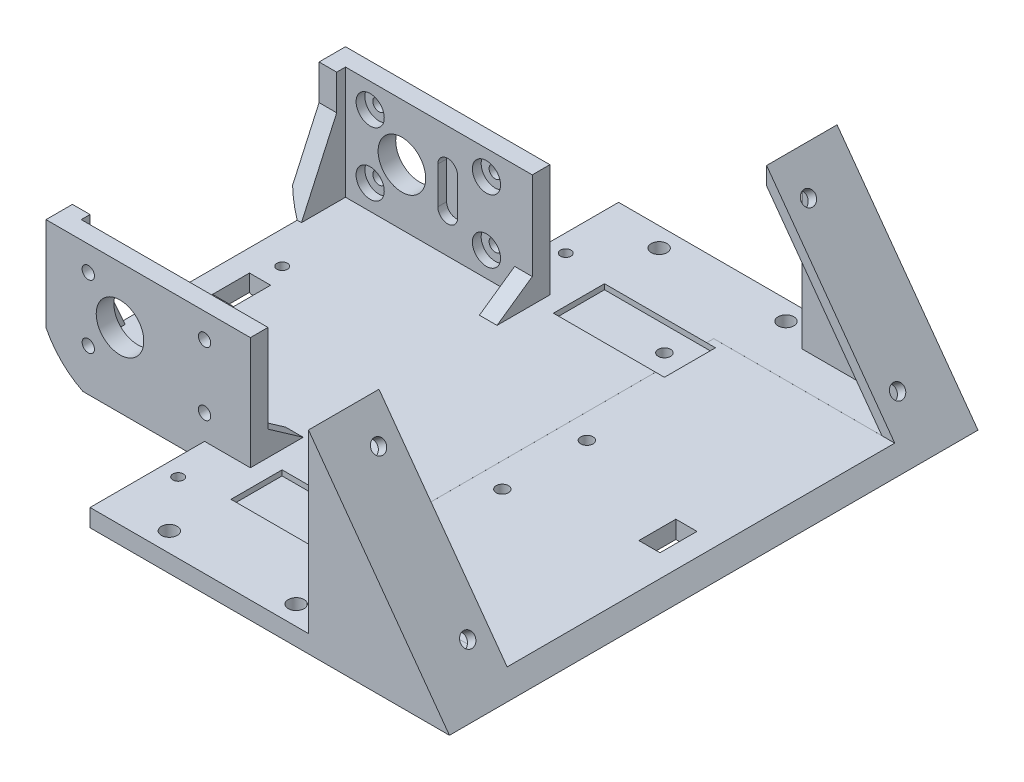
SolidWorks part; units mm, degrees
ref_plane "Front Plane" through (0, 0, 0) normal (0, 0, 1) x (1, 0, 0)
ref_plane "Top Plane" through (0, 0, 0) normal (0, 1, 0) x (1, 0, 0)
ref_plane "Right Plane" through (0, 0, 0) normal (1, 0, 0) x (0, 0, -1)
sketch "Sketch1" plane through (0, 0, 0) normal (0, 1, 0) x (1, 0, 0)
  line L0 (-25, 75) -> (-25, 42.5)
  line L1 (-25, -75) -> (77, -75)
  line L2 (-70, -42.5) -> (-70, 42.5)
  line L3 (-25, 75) -> (77, 75)
  line L4 (77, -75) -> (77, 75)
  line L7 (-25, 42.5) -> (-70, 42.5)
  line L8 (2, 0) -> (77, 0) construction
  line L9 (-25, -42.5) -> (-70, -42.5)
  line L10 (-25, -75) -> (-25, -42.5)
  point P0 (0, 0)
  dimension "D1" = 150
  dimension "D2" = 102
  dimension "D3" = 85
  dimension "D4" = 45
  dimension "D5" = 75
  dimension "D6" = 32.5
  dimension "D7" = 32.5
extrude "Boss-Extrude1" add sketch "Sketch1" along normal blind 5
sketch "Sketch3" plane through (0, 5, 0) normal (0, 1, 0) x (1, 0, 0)
  line L2 (-65, 25) -> (-70, 25)
  line L3 (-25, 42.5) -> (-70, 42.5) construction
  line L6 (-65, 25) -> (-65, 37.5)
  line L8 (0, 0) -> (-70, 0) construction
  line L9 (-70, 42.5) -> (-70, -42.5) construction
  line L17 (-65, 37.5) -> (-17, 37.5)
  line L18 (-12, 37.5) -> (-12, 42.5)
  line L19 (-12, 42.5) -> (-25, 42.5)
  line L20 (-25, 42.5) -> (-65, 42.5)
  line L28 (-12, 37.5) -> (-12, 27.5)
  line L29 (-12, 27.5) -> (-17, 27.5)
  line L30 (-17, 27.5) -> (-17, 37.5)
  line L40 (-70, -42.5) -> (-65, -42.5)
  line L41 (-70, 25) -> (-70, 42.5)
  line L42 (-70, 42.5) -> (-65, 42.5)
  line L43 (-70, -25) -> (-70, -42.5)
  line L44 (-17, -27.5) -> (-17, -37.5)
  line L45 (-12, -27.5) -> (-17, -27.5)
  line L46 (-12, -37.5) -> (-12, -27.5)
  line L47 (-25, -42.5) -> (-65, -42.5)
  line L48 (-12, -42.5) -> (-25, -42.5)
  line L49 (-12, -37.5) -> (-12, -42.5)
  line L50 (-65, -37.5) -> (-17, -37.5)
  line L51 (-65, -25) -> (-65, -37.5)
  line L52 (-65, -25) -> (-70, -25)
  line M11 (-70, -42.5) -> (-25, -42.5)
  dimension "D1" = 0
  dimension "D2" = 5
  dimension "D3" = 48
  dimension "D4" = 5
  dimension "D6" = 5
  dimension "D7" = 15
  dimension "D8" = 5
  dimension "D9" = 5
extrude "Boss-Extrude2" add sketch "Sketch3" along normal blind 32 contours M11 | L6 L17 L30 L29 L28 L18 L19 L20 L42 L41 L2 region at (-41.823, 5, 37.7096)
sketch "Sketch5" plane through (-70, 0, 0) normal (-1, 0, 0) x (0, 0, 1)
  line L0 (-25, 37) -> (-35, 37)
  line L1 (-25, 37) -> (-42.5, 37) construction
  line L2 (-35, 37) -> (-35, 27)
  line L3 (-35, 27) -> (-25, 5)
  line L4 (-25, 5) -> (-25, 37)
  line L5 (0, 0) -> (0, 35) construction
  line L6 (25, 5) -> (25, 37)
  line L7 (35, 27) -> (25, 5)
  line L8 (35, 37) -> (35, 27)
  line L9 (25, 37) -> (35, 37)
  dimension "D1" = 10
  dimension "D2" = 10
extrude "Cut-Extrude2" cut sketch "Sketch5" against normal blind 5
sketch "Sketch6" plane through (-12, 0, 0) normal (1, 0, 0) x (0, 0, -1)
  line L0 (-27.5, 37) -> (-37.5, 37)
  line L1 (-27.5, 37) -> (-42.5, 37) construction
  line L2 (-37.5, 37) -> (-37.5, 12)
  line L3 (-37.5, 12) -> (-27.5, 5)
  line L4 (-27.5, 5) -> (-27.5, 37)
  line L5 (0, 0) -> (0, 35) construction
  line L6 (37.5, 12) -> (27.5, 5)
  line L7 (37.5, 37) -> (37.5, 12)
  line L8 (27.5, 37) -> (37.5, 37)
  line L9 (27.5, 5) -> (27.5, 37)
  dimension "D1" = 10
  dimension "D2" = 25
extrude "Cut-Extrude3" cut sketch "Sketch6" against normal blind 5
sketch "Sketch7" plane through (0, 0, -42.5) normal (0, 0, -1) x (-1, 0, 0)
  line L0 (70, 37) -> (70, 0) construction
  line L1 (70, 37) -> (12, 37) construction
  line L2 (70, 37) -> (70, 0) construction
  circle A0 centre (49, 21) radius 6.75
  circle A1 centre (25, 30) radius 1.75
  circle A2 centre (25, 12) radius 1.75
  circle A3 centre (58, 30) radius 1.75
  circle A4 centre (58, 12) radius 1.75
  dimension "D1" = 21
  dimension "D2" = 13.5
  dimension "D3" = 16
  dimension "D4" = 3.5
  dimension "D5" = 7
  dimension "D6" = 12
  dimension "D7" = 3.5
  dimension "D10" = 3.5
  dimension "D12" = 3.5
  dimension "D13" = 7
  dimension "D14" = 18
  dimension "D15" = 12
  dimension "D8" = 33
  dimension "D9" = 18
  dimension "D11" = 33
extrude "Đục lỗ động cơ" cut sketch "Sketch7" against normal through all
sketch "Sketch8" plane through (0, 5, 0) normal (0, 1, 0) x (1, 0, 0)
  line L0 (77, -75) -> (77, -65)
  line L1 (77, -75) -> (77, 75) construction
  line L2 (77, -65) -> (37, -65)
  line L3 (37, -65) -> (37, -75)
  line L4 (-25, -75) -> (77, -75) construction
  line L5 (37, -75) -> (77, -75)
  line L6 (77, 0) -> (0, 0) construction
  line L7 (37, 75) -> (77, 75)
  line L8 (37, 65) -> (37, 75)
  line L9 (77, 65) -> (37, 65)
  line L10 (77, 75) -> (77, 65)
  dimension "D1" = 10
  dimension "D2" = 40
extrude "Boss-Extrude3" add sketch "Sketch8" along normal blind 55
sketch "Sketch9" plane through (0, 0, -75) normal (0, 0, -1) x (-1, 0, 0)
  line L4 (-77, 0) -> (-37, 55.0553)
  line L5 (-37, 60) -> (-37, 5) construction
  line L6 (-37, 55.0553) -> (-37, 60)
  line L7 (-37, 60) -> (-77, 60)
  line L8 (-77, 60) -> (-77, 0)
  line L9 (-77, 0) -> (25, 0) construction
  dimension "D1" = 54
extrude "Cut-Extrude5" cut sketch "Sketch9" against normal through all
sketch "Sketch10" plane through (0, 0, 0) normal (0, -1, 0) x (-1, 0, 0)
  line L0 (25, -75) -> (-77, -75) construction
  line L2 (70, 42.5) -> (70, -42.5) construction
  line L3 (25, -42.5) -> (25, -75) construction
  line L4 (70, 0) -> (-77, 0) construction
  line L5 (-77, -75) -> (-77, 75) construction
  circle A0 centre (-29, -12) radius 1.75
  circle A2 centre (-17, -46) radius 1.75
  circle A3 centre (-17, 46) radius 1.75
  circle A4 centre (-29, 12) radius 1.75
  circle A5 centre (-28, -69.5) radius 2.25
  circle A6 centre (8, -69.5) radius 2.25
  circle A7 centre (8, 69.5) radius 2.25
  circle A8 centre (-28, 69.5) radius 2.25
  dimension "D1" = 63
  dimension "D5" = 3.5
  dimension "D6" = 4.5
  dimension "D7" = 29
  dimension "D8" = 3.5
  dimension "D9" = 42
  dimension "D10" = 4.5
  dimension "D2" = 5.5
  dimension "D4" = 5.5
  dimension "D11" = 53
  dimension "D12" = 17
  dimension "D3" = 99
extrude "Đục Lỗ Đế" cut sketch "Sketch10" against normal through all
sketch "Sketch11" plane through (0, 0, -75) normal (0, 0, -1) x (-1, 0, 0)
  line L0 (-37, 55.0553) -> (-37, 50.0553)
  line L1 (-37, 55.0553) -> (-37, 5) construction
  line L2 (-37, 50.0553) -> (-73.3673, 0)
  line L3 (-77, 0) -> (25, 0) construction
  line L4 (-73.3673, 0) -> (-77, 0)
  line L5 (-77, 0) -> (-37, 55.0553)
  dimension "D1" = 54
extrude "Boss-Extrude4" add sketch "Sketch11" against normal through all
sketch "Sketch13" plane through (50.3972, 36.6157, 0) normal (0.809, 0.5878, 0) x (0, 0, -1)
  line L0 (-66.2591, 11.2877) -> (-63.4854, 6.3356)
  line L1 (-52.4057, -31.0399) -> (-48.867, -10.0267)
  line L2 (-48.867, -10.0267) -> (-4.2777, -9.567)
  line L3 (-4.2777, -9.567) -> (-7.732, -31.4993)
  line L4 (-7.732, -31.4993) -> (-52.4057, -31.0399)
  line L5 (3.9481, -10.0267) -> (7.33, -31.4995)
  line L6 (7.33, -31.4995) -> (53.0101, -31.4995)
  line L7 (53.0101, -31.4995) -> (49.5558, -9.5672)
  line L8 (49.5558, -9.5672) -> (3.9481, -10.0267)
  line L9 (-48.867, -10.0267) -> (-7.732, -31.4993) construction
  line L10 (-4.2777, -9.567) -> (-52.4057, -31.0399) construction
  line L11 (3.9481, -10.0267) -> (53.0101, -31.4995) construction
  line L12 (49.5558, -9.5672) -> (7.33, -31.4995) construction
  line L13 (3.9481, -10.0267) -> (-7.732, -31.4993) construction
  line L14 (7.33, -31.4995) -> (-4.2777, -9.567) construction
  line L15 (3.9481, -10.0267) -> (-4.2777, -9.567) construction
  line L16 (-7.732, -31.4993) -> (7.33, -31.4995) construction
  line L18 (-75, -45.2595) -> (75, -45.2595) construction
  line L19 (75, -45.2595) -> (75, 22.7926) construction
  dimension "D1" = 15.062
  dimension "D2" = 44.5893
  dimension "D3" = 45.6077
  dimension "D4" = 21.9323
  dimension "D5" = 21.4727
  dimension "D6" = 21.0132
  dimension "D7" = 52.7009
  dimension "D8" = 46.4022
  dimension "D9" = 53.5552
  dimension "D10" = 47.582
  dimension "D11" = 45.6801
  dimension "D12" = 21.7374
  dimension "D13" = 98.361
  dimension "D14" = 100.15
  dimension "D15" = 80.459
  dimension "D16" = 81.03
  dimension "D17" = 98.95
  dimension "D18" = 81.05
  dimension "D19" = 98.373
  dimension "D20" = 18.94
  dimension "D21" = 19.594
  dimension "D22" = 13.76
  dimension "D23" = 67.67
extrude "Cut-Extrude7" cut sketch "Sketch13" against normal blind 5 contours L4 L3 L2 L1 | L7 L8 L5 L6 region at (62.4718, 19.9963, 28.1629) region at (62.5336, 19.9112, -28.5416)
sketch "Sketch14" plane through (0, 0, 37.5) normal (0, 0, -1) x (-1, 0, 0)
  line L0 (36, 26.25) -> (36, 15.75) construction
  line L1 (38.8, 26.25) -> (38.8, 15.75)
  line L2 (33.2, 26.25) -> (33.2, 15.75)
  line L4 (65, 37) -> (12, 37) construction
  circle A0 centre (58, 30) radius 4
  circle A1 centre (25, 30) radius 4
  circle A2 centre (25, 12) radius 4
  circle A3 centre (58, 12) radius 4
  arc A4 (38.8, 26.25) -> (33.2, 26.25) centre (36, 26.25) ccw
  arc A5 (33.2, 15.75) -> (38.8, 15.75) centre (36, 15.75) ccw
  point P14 (36, 21)
  dimension "D1" = 8
  dimension "D2" = 2.8
  dimension "D4" = 16
  dimension "D5" = 11
  dimension "D3" = 10.5
extrude "Cut-Extrude8" cut sketch "Sketch14" against normal blind 2.5
sketch "Sketch15" plane through (0, 0, -37.5) normal (0, 0, 1) x (1, 0, 0)
  line L0 (-36, 26.25) -> (-36, 15.75) construction
  line L1 (-33.2, 26.25) -> (-33.2, 15.75)
  line L2 (-38.8, 26.25) -> (-38.8, 15.75)
  line L3 (-65, 37) -> (-12, 37) construction
  circle A0 centre (-25, 30) radius 4
  circle A1 centre (-25, 12) radius 4
  circle A2 centre (-58, 12) radius 4
  circle A3 centre (-58, 30) radius 4
  arc A4 (-33.2, 26.25) -> (-38.8, 26.25) centre (-36, 26.25) ccw
  arc A5 (-38.8, 15.75) -> (-33.2, 15.75) centre (-36, 15.75) ccw
  point P14 (-36, 21)
  dimension "D1" = 8
  dimension "D2" = 2.8
  dimension "D3" = 10.5
  dimension "D4" = 16
  dimension "D5" = 11
extrude "Cut-Extrude9" cut sketch "Sketch15" against normal blind 2.5
sketch "Sketch16" plane through (0, 0, 0) normal (0, -1, 0) x (-1, 0, 0)
  line L0 (25, -75) -> (-77, -75) construction
  line L1 (60, 5.25) -> (54, 5.25)
  line L2 (60, 5.25) -> (60, -5.25)
  line L3 (60, -5.25) -> (54, -5.25)
  line L4 (54, 5.25) -> (54, -5.25)
  line L5 (-61, 5.25) -> (-67, 5.25)
  line L6 (-61, 5.25) -> (-61, -5.25)
  line L7 (-61, -5.25) -> (-67, -5.25)
  line L8 (-67, 5.25) -> (-67, -5.25)
  line L9 (-77, -75) -> (-77, 75) construction
  line L10 (70, 42.5) -> (70, -42.5) construction
  dimension "D1" = 10.5
  dimension "D2" = 6
  dimension "D3" = 10.5
  dimension "D4" = 6
  dimension "D5" = 69.75
  dimension "D6" = 69.75
  dimension "D7" = 10
  dimension "D8" = 10
extrude "Cut-Extrude10" cut sketch "Sketch16" against normal blind 5
ref_plane "Plane2" through (77, 0, 0) normal (-1, 0, 0) x (0, 0, 1)
sketch "Sketch20" plane through (77, 0, 0) normal (-1, 0, 0) x (0, 0, 1)
  line L0 (75, 55.0553) -> (55, 55.0553)
  line L1 (55, 55.0553) -> (55, 4.9953)
  line L2 (55, 4.9953) -> (-55, 4.9953)
  line L3 (-55, 4.9953) -> (-55, 55.0553)
  line L4 (55, 55.0553) -> (-55, 55.0553)
  line L5 (-75, 0) -> (-75, 55.0553) construction
  dimension "D1" = 20
  dimension "D2" = 50.06
  dimension "D3" = 20
extrude "Cut-Extrude11" cut sketch "Sketch20" along normal blind 55 contours L1 L4 L3 L2 region at (77, 30.0253, 0)
sketch "Sketch22" plane through (50.3972, 36.6157, 0) normal (0.809, 0.5878, 0) x (0, 0, -1)
  line L0 (-55, -39.085) -> (-55, 22.7926) construction
  line L1 (-55, -8.89) -> (-55, -39.085) construction
  line L2 (-75, 22.7926) -> (-55, 22.7926) construction
  line L3 (-75, -45.2595) -> (75, -45.2595) construction
  line L4 (0, -39.085) -> (0, 36.7715) construction
  line L5 (55, -39.085) -> (-55, -39.085) construction
  circle A0 centre (-61, 12.7926) radius 2
  circle A1 centre (-61, -30.2595) radius 2
  circle A2 centre (61, -30.2595) radius 2
  circle A3 centre (61, 12.7926) radius 2
  dimension "D1" = 4
  dimension "D2" = 4
  dimension "D3" = 6
  dimension "D4" = 6
  dimension "D5" = 10
  dimension "D6" = 15
extrude "Cut-Extrude12" cut sketch "Sketch22" against normal blind 5
sketch "Sketch23" plane through (0, 5, 0) normal (0, 1, 0) x (1, 0, 0)
  line L0 (-25, 75) -> (-25, 42.5) construction
  line L1 (-7, 38.5) -> (-6, 38.5)
  line L2 (-7, 38.5) -> (-7, 53)
  line L3 (-7, 53) -> (24.5, 53)
  line L4 (24.5, 38.5) -> (24.5, 53)
  line L5 (37, 75) -> (-25, 75) construction
  line L8 (24.5, -38.5) -> (24.5, -53)
  line L9 (-7, -53) -> (24.5, -53)
  line L10 (-7, -38.5) -> (-7, -53)
  line L11 (-7, -38.5) -> (-6, -38.5)
  line L28 (0, 38.5) -> (24.5, 38.5)
  line L29 (0, -38.5) -> (24.5, -38.5)
  line L37 (-6, 38.5) -> (0, 38.5)
  line L38 (-6, -38.5) -> (0, -38.5)
  dimension "D1" = 14.5
  dimension "D2" = 31.5
  dimension "D3" = 18
  dimension "D4" = 22
  dimension "D9" = 6
extrude "Cut-Extrude13" cut sketch "Sketch23" against normal blind 1.5
sketch "Sketch25" plane through (0, 0, 42.5) normal (0, 0, 1) x (1, 0, 0)
  line L0 (-70, 10.4525) -> (-70, 0)
  line L1 (-70, 37) -> (-70, 0) construction
  line L2 (-70, 0) -> (-59.5475, 0)
  line L3 (-70, 0) -> (-25, 0) construction
  arc A0 (-70, 10.4525) -> (-59.5475, 0) centre (-49, 21) ccw
  dimension "D1" = 23.5
extrude "Cut-Extrude15" cut sketch "Sketch25" against normal blind 89
sketch "Sketch26" plane through (0, 0, 0) normal (0, -1, 0) x (1, 0, 0)
  line L0 (-66.2119, -25) -> (-66.2119, 25) construction
  line L1 (-54, 5.25) -> (-59.5475, 5.25) construction
  line L2 (-60, 0) -> (-54, 0) construction
  line L3 (-60, 5.25) -> (-60, -5.25) construction
  line L4 (-54, -5.25) -> (-54, 5.25) construction
  line L5 (-25, -75) -> (-25, -42.5) construction
  line L6 (77, -75) -> (-25, -75) construction
  circle A0 centre (-57.0119, 11.55) radius 1.5
  circle A1 centre (-57.0119, -11.55) radius 1.5
  circle A3 centre (-20, -55) radius 1.5
  circle A4 centre (-20, 55) radius 1.5
  dimension "D1" = 9.2
  dimension "D3" = 3
  dimension "D4" = 5
  dimension "D5" = 20
  dimension "D6" = 3
  dimension "D2" = 6.3
extrude "Cut-Extrude16" cut sketch "Sketch26" against normal blind 5
